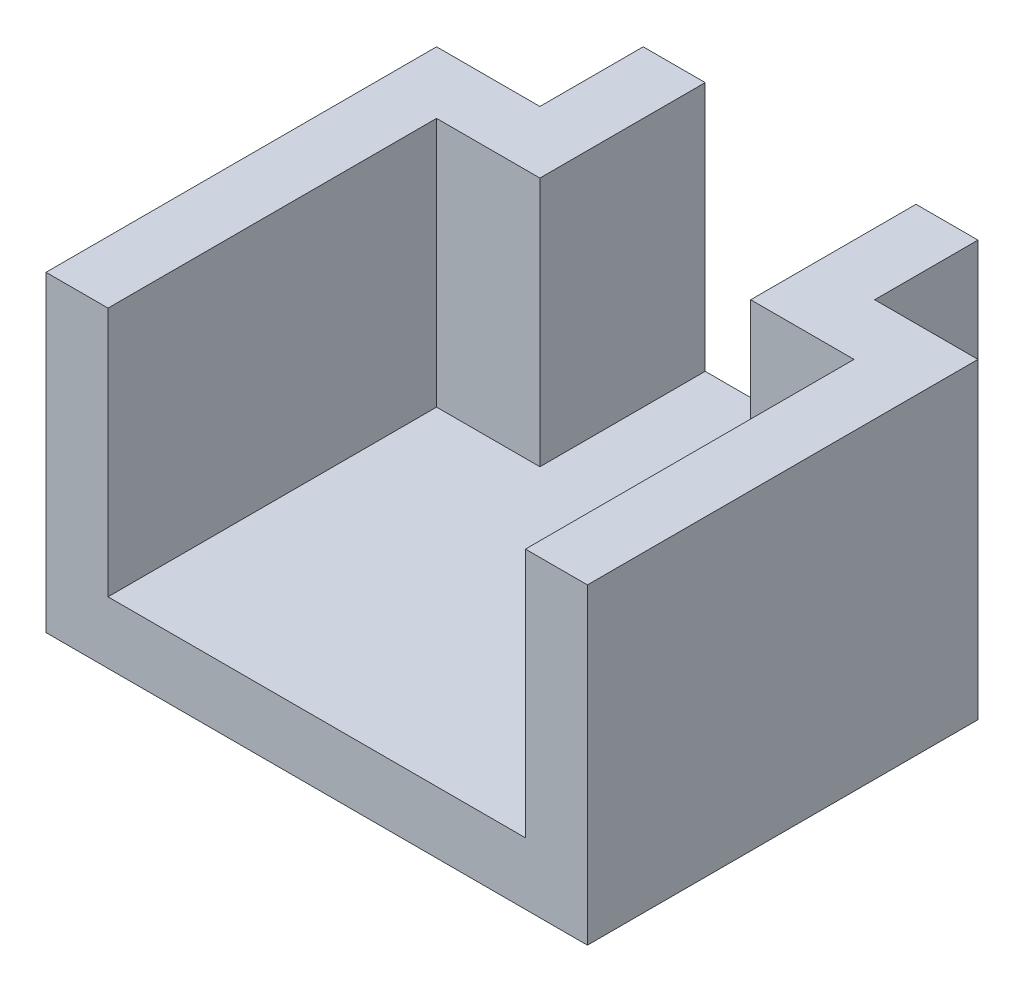
SolidWorks part; units mm, degrees
note: The reader was unsure of these and kept them because the rebuilt part matched: shared geometry of "Sketch1<3>".
ref_plane "Front Plane" through (0, 0, 0) normal (0, 0, 1) x (1, 0, 0)
ref_plane "Top Plane" through (0, 0, 0) normal (0, 1, 0) x (1, 0, 0)
ref_plane "Right Plane" through (0, 0, 0) normal (1, 0, 0) x (0, 0, -1)
sketch "Sketch1" plane through (0, 0, 0) normal (0, 1, 0) x (1, 0, 0)
  line L0 (10.1, 0) -> (10.1, -23.9)
  line L2 (0, 0) -> (0, -23.9)
  line L4 (20.2, 0) -> (20.2, -23.9)
  line L6 (0, 0) -> (0, -23.9)
  line L9 (20.2, 0) -> (20.2, -23.9)
  line L10 (0, 0) -> (20.2, 0)
  line L11 (20.2, 0) -> (20.2, -23.9)
  line L12 (0, -23.9) -> (20.2, -23.9)
  line L13 (0, 0) -> (-3, 0)
  line L14 (0, 0) -> (0, -23.9)
  line L15 (0, -23.9) -> (-3, -23.9)
  line L16 (-3, 0) -> (-3, -23.9)
  line L17 (20.2, -23.9) -> (23.2, -23.9)
  line L18 (23.2, 0) -> (23.2, -23.9)
  line L19 (20.2, 0) -> (23.2, 0)
  line L20 (2, -8) -> (0, -8)
  line L21 (2, -8) -> (2, 0)
  line L22 (2, 0) -> (5, 0)
  line L23 (5, 0) -> (5, -8)
  line L24 (5, -8) -> (2, -8)
  line L25 (5, -8) -> (15.2, -8)
  line L26 (20.2, -8) -> (23.2, -8)
  line L27 (15.2, -8) -> (18.2, -8)
  line L28 (15.2, 0) -> (15.2, -8)
  line L29 (18.2, -8) -> (18.2, 0)
  line L30 (0, -8) -> (-3, -8)
  line L31 (18.2, -8) -> (20.2, -8)
  line L32 (18.2, -8) -> (23.2, -8)
  line L33 (2, -8) -> (-3, -8)
  line L34 (2, -8) -> (2, -5)
  line L35 (2, -5) -> (-3, -5)
  line L36 (-3, -8) -> (-3, -5)
  line L37 (23.2, -8) -> (23.2, -5)
  line L38 (18.2, -5) -> (23.2, -5)
  line L39 (18.2, -8) -> (18.2, -5)
  point P4 (3.5, -8)
  point P26 (10.1, -8)
  dimension "D1" = 23.9
  dimension "D2" = 20.2
  dimension "D3" = 3
  dimension "D4" = 10.2
  dimension "D5" = 8
  dimension "D6" = 3
  dimension "D7" = 3
  dimension "D8" = 5
extrude "Boss-Extrude1" add sketch "Sketch1" along normal blind 3
extrude "Boss-Extrude2" add sketch "Sketch1<3>" along normal blind 15.1 contours L13 L16 L15 L2 | L19 L4 L17 L18 | L24 L23 L10 L21 | L27 L29 L10 L28 | L21 L35 L14 L20 | L38 L29 L31 L11 | L14 L30 L16 L15 | L26 L11 L17 L18
sketch "Sketch1<3>" plane through (0, 0, 0) normal (0, 1, 0) x (1, 0, 0) same geometry as "Sketch1"
